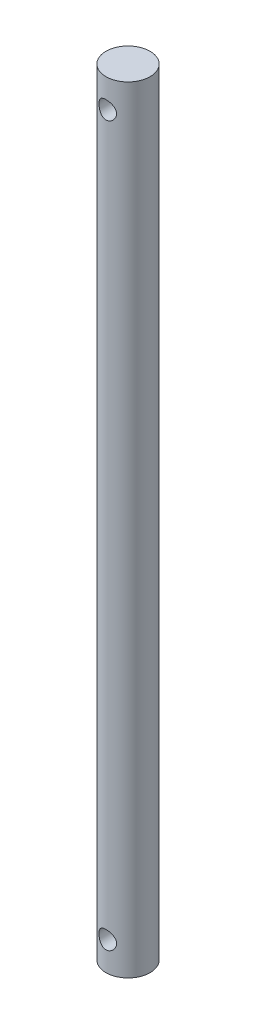
SolidWorks part; units mm, degrees
ref_plane "Alzado" through (0, 0, 0) normal (0, 0, 1) x (1, 0, 0)
ref_plane "Planta" through (0, 0, 0) normal (0, 1, 0) x (1, 0, 0)
ref_plane "Vista lateral" through (0, 0, 0) normal (1, 0, 0) x (0, 0, -1)
sketch "Croquis1" plane through (0, 0, 0) normal (0, 1, 0) x (1, 0, 0)
  circle A0 centre (0, 0) radius 5
  dimension "D1" = 10
extrude "Saliente-Extruir1" add sketch "Croquis1" along normal blind 339
sketch "Croquis8" plane through (0, 0, 0) normal (0, -1, 0) x (1, 0, 0)
  circle A0 centre (0, 0) radius 6.2858
extrude "Cortar-Extruir5" cut sketch "Croquis8" against normal blind 163
sketch "Croquis9" plane through (0, 0, 0) normal (0, 0, 1) x (1, 0, 0)
  line L0 (0, 339) -> (0, 332.5) construction
  line L2 (17.7704, 172.714) -> (17.8333, 172.7768) construction
  line L3 (5, 339) -> (-5, 339) construction
  circle A0 centre (0, 332.5) radius 2
  dimension "D2" = 4
  dimension "D1" = 6.5
extrude "Cortar-Extruir6" cut sketch "Croquis9" against normal blind 10 and the other way blind 10
sketch "Croquis10" plane through (0, 0, 0) normal (0, 0, 1) x (1, 0, 0)
  line L0 (0, 163) -> (0, 169.5) construction
  line L2 (-5, 163) -> (5, 163) construction
  circle A0 centre (0, 169.5) radius 2
  point P3 (0, 0)
  point P4 (0, 163)
  dimension "D2" = 4
  dimension "D3" = 6.5
extrude "Cortar-Extruir7" cut sketch "Croquis10" against normal blind 10 and the other way blind 10
